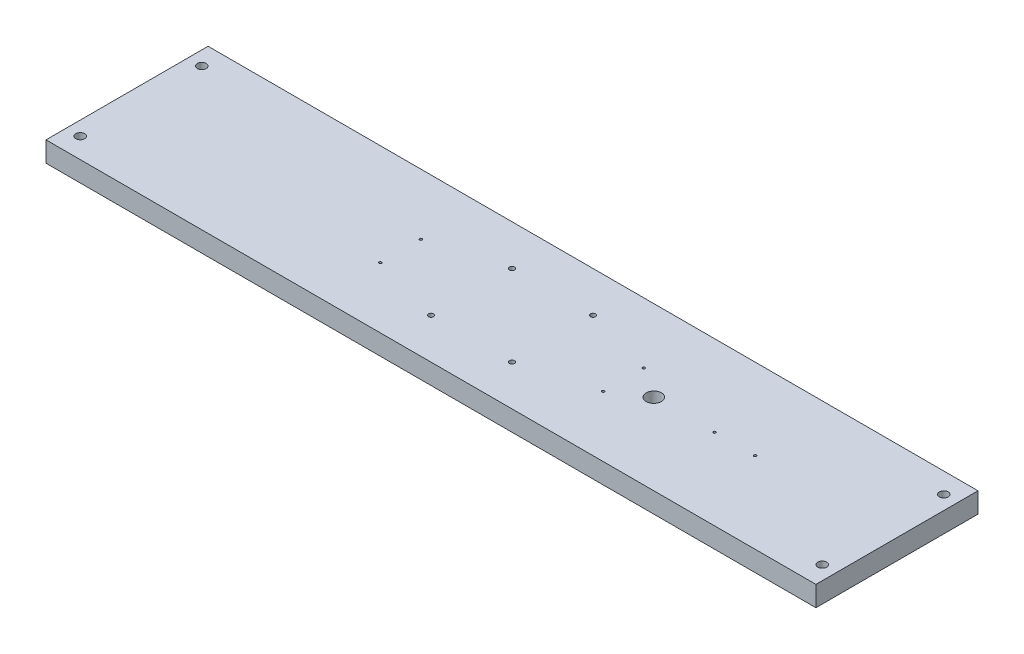
SolidWorks part; units mm, degrees
ref_plane "Front Plane" through (0, 0, 0) normal (0, 0, 1) x (1, 0, 0)
ref_plane "Top Plane" through (0, 0, 0) normal (0, 1, 0) x (1, 0, 0)
ref_plane "Right Plane" through (0, 0, 0) normal (1, 0, 0) x (0, 0, -1)
sketch "Sketch1" plane through (0, 0, 0) normal (0, 1, 0) x (1, 0, 0)
  line L1 (-241.3, -50.8) -> (241.3, -50.8)
  line L2 (-241.3, -50.8) -> (-241.3, 50.8)
  line L3 (-241.3, 50.8) -> (241.3, 50.8)
  line L4 (241.3, -50.8) -> (241.3, 50.8)
  line L5 (-241.3, -50.8) -> (241.3, 50.8) construction
  line L6 (-241.3, 50.8) -> (241.3, -50.8) construction
  point P0 (0, 0)
  dimension "D1" = 101.6
  dimension "D2" = 482.6
extrude "Boss-Extrude1" add sketch "Sketch1" along normal blind 12.7
sketch "Sketch2" plane through (0, 12.7, 0) normal (0, 1, 0) x (1, 0, 0)
  line L0 (0, 50.8) -> (0, -50.8) construction
  line L1 (241.3, 50.8) -> (-241.3, 50.8) construction
  line L2 (-241.3, -50.8) -> (241.3, -50.8) construction
  circle A0 centre (-232.5624, 38.1) radius 2.7813
  circle A1 centre (-232.5624, -38.1) radius 2.7813
  circle A2 centre (232.5624, 38.1) radius 2.7813
  circle A3 centre (232.5624, -38.1) radius 2.7813
  dimension "D1" = 465.1248
  dimension "D2" = 5.5626
  dimension "D3" = 5.5626
  dimension "D4" = 5.5626
  dimension "D5" = 5.5626
  dimension "D6" = 76.2
  dimension "D7" = 12.7
extrude "Cut-Extrude1" cut sketch "Sketch2" against normal through all
sketch "Sketch3" plane through (0, 12.7, 0) normal (0, 1, 0) x (1, 0, 0)
  line L1 (-25.4, -25.4) -> (25.4, -25.4) construction
  line L2 (-25.4, -25.4) -> (-25.4, 25.4) construction
  line L3 (-25.4, 25.4) -> (25.4, 25.4) construction
  line L4 (25.4, -25.4) -> (25.4, 25.4) construction
  line L5 (-25.4, -25.4) -> (25.4, 25.4) construction
  line L6 (-25.4, 25.4) -> (25.4, -25.4) construction
  circle A0 centre (-25.4, 25.4) radius 1.5875
  circle A1 centre (25.4, 25.4) radius 1.5875
  circle A2 centre (25.4, -25.4) radius 1.5875
  circle A3 centre (-25.4, -25.4) radius 1.5875
  point P0 (0, 0)
  dimension "D3" = 3.175
  dimension "D4" = 3.175
  dimension "D5" = 3.175
  dimension "D6" = 3.175
  dimension "D1" = 50.8
  dimension "D2" = 50.8
extrude "Cut-Extrude2" cut sketch "Sketch3" against normal through all
sketch "Sketch4" plane through (0, 12.7, 0) normal (0, 1, 0) x (1, 0, 0)
  line L0 (-241.3, 0) -> (241.3, 0) construction
  line L1 (-241.3, 50.8) -> (-241.3, -50.8) construction
  line L2 (241.3, -50.8) -> (241.3, 50.8) construction
  line L3 (0, 50.8) -> (0, -50.8) construction
  line L4 (241.3, 50.8) -> (-241.3, 50.8) construction
  line L5 (-241.3, -50.8) -> (241.3, -50.8) construction
  line L7 (-69.85, -12.7) -> (69.85, -12.7) construction
  line L8 (-69.85, -12.7) -> (-69.85, 12.7) construction
  line L9 (-69.85, 12.7) -> (69.85, 12.7) construction
  line L10 (69.85, -12.7) -> (69.85, 12.7) construction
  line L11 (-69.85, -12.7) -> (69.85, 12.7) construction
  line L12 (-69.85, 12.7) -> (69.85, -12.7) construction
  circle A4 centre (-69.85, 12.7) radius 0.7937
  circle A5 centre (-69.85, -12.7) radius 0.7937
  circle A6 centre (69.85, -12.7) radius 0.7937
  circle A7 centre (69.85, 12.7) radius 0.7937
  point P20 (0, 0)
  dimension "D11" = 1.5875
  dimension "D12" = 1.5875
  dimension "D13" = 1.5875
  dimension "D14" = 1.5875
  dimension "D9" = 25.4
  dimension "D10" = 139.7
extrude "Cut-Extrude3" cut sketch "Sketch4" against normal through all
sketch "Sketch5" plane through (0, 12.7, 0) normal (0, 1, 0) x (1, 0, 0)
  circle A0 centre (127, 0) radius 0.7938
  circle A1 centre (152.4, 0) radius 0.7937
  dimension "D2" = 1.5875
  dimension "D4" = 1.5875
  dimension "D1" = 25.4
  dimension "D3" = 127
extrude "Cut-Extrude4" cut sketch "Sketch5" against normal through all
sketch "Sketch6" plane through (0, 12.7, 0) normal (0, 1, 0) x (1, 0, 0)
  circle A2 centre (88.9, 0) radius 4.7625
  point P2 (101.6, 0)
  dimension "D2" = 88.9
  dimension "D1" = 9.525
extrude "Cut-Extrude5" cut sketch "Sketch6" against normal through all
